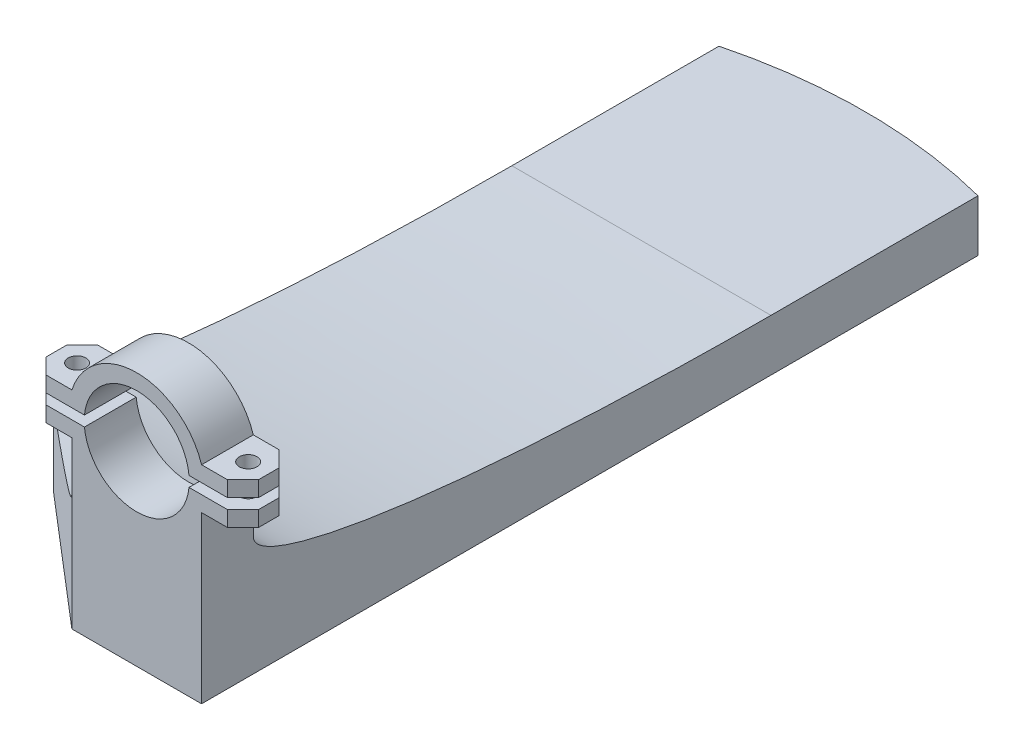
SolidWorks part; units mm, degrees
material "PET"
ref_plane "Front Plane" through (0, 0, 0) normal (0, 0, 1) x (1, 0, 0)
ref_plane "Top Plane" through (0, 0, 0) normal (0, 1, 0) x (1, 0, 0)
ref_plane "Right Plane" through (0, 0, 0) normal (1, 0, 0) x (0, 0, -1)
sketch "Sketch1" plane through (0, 0, 0) normal (0, 0, 1) x (1, 0, 0)
  line L0 (55, 0) -> (-55, 0) construction
  line L1 (-20.5269, -1) -> (-10.1006, -1)
  line L3 (-20.5269, 1) -> (-10.1006, 1)
  line L5 (-27.2535, 0) -> (26.6027, 0) construction
  line L6 (10.1006, 1) -> (20.5269, 1)
  line L7 (-12.5269, 4) -> (-20.5269, 4)
  line L9 (-10.1006, 1) -> (-20.5269, 1)
  line L10 (-20.5269, 4) -> (-20.5269, 1)
  line L11 (-10.1006, -1) -> (-20.5269, -1)
  line L12 (-20.5269, -4) -> (-20.5269, -1)
  line L13 (-12.5269, -4) -> (-20.5269, -4)
  line L15 (0, -55) -> (0, 55) construction
  line L17 (12.5269, -4) -> (20.5269, -4)
  line L18 (20.5269, -4) -> (20.5269, -1)
  line L19 (10.1006, -1) -> (20.5269, -1)
  line L20 (10.1006, 1) -> (20.5269, 1)
  line L21 (20.5269, 4) -> (20.5269, 1)
  line L22 (12.5269, 4) -> (20.5269, 4)
  line L24 (10.1006, 1) -> (20.5269, 1)
  line L25 (20.5269, -1) -> (10.1006, -1)
  line L26 (-20.5269, 1) -> (-10.1006, 1)
  line L27 (-10.1006, -1) -> (-20.5269, -1)
  line L28 (10.1006, -1) -> (20.5269, -1)
  line L31 (-12.5269, -4) -> (-12.5269, -36)
  line L32 (-12.5269, -36) -> (12.5269, -36)
  line L33 (12.5269, -4) -> (12.5269, -36)
  arc A0 (-10.1006, -1) -> (10.1006, -1) centre (0, 0) ccw
  arc A3 (10.1006, 1) -> (-10.1006, 1) centre (0, 0) ccw
  arc A4 (12.5269, 4) -> (-12.5269, 4) centre (0, 0) ccw
  dimension "D1" = 2
  dimension "D2" = 20.3
  dimension "D3" = 3
  dimension "D4" = 8
  dimension "D5" = 3
  dimension "D6" = 32
extrude "Boss-Extrude1" add sketch "Sketch1" along normal mid plane 10 contours L22 A4 L7 L10 L3 A3 L6 L21 | L13 L17 L18 L19 A0 L1 L12 region at (0, -19.9858, 0) region at (-20.0987, 2.5, 0)
sketch "Sketch2" plane through (0, 4, 0) normal (0, 1, 0) x (1, 0, 0)
  line L0 (-20.5269, 5) -> (-12.5269, -5) construction
  line L1 (-20.5269, -5) -> (-12.5269, 5) construction
  line L2 (20.5269, 5) -> (12.5269, -5) construction
  line L3 (20.5269, -5) -> (12.5269, 5) construction
  point P8 (-16.5269, 0)
  point P17 (16.5269, 0)
hole_wizard "M3 Clearance Hole1" positions "Sketch3" profile "Sketch4" hole size "M3" standard "ANSI Metric" end condition through all
sketch "Sketch3" plane through (0, 4, 0) normal (0, 1, 0) x (1, 0, 0)
  point P0 (-16.5269, 0)
  point P3 (16.5269, 0)
sketch "Sketch4" plane through (-16.5269, 4, 0) normal (1, 0, 0) x (0, 0, 1)
  line L0 (0, 0) -> (0, 40)
  line L1 (0, 40) -> (1.7, 40)
  line L2 (1.7, 40) -> (1.7, 0)
  line L5 (1.7, 0) -> (0, 0)
  line L11 (0, -6.35) -> (0, 107.95) construction
  dimension "Thru Hole Dia." = 3.4
  dimension "Thru Hole Depth" = 40
sketch "Sketch5" plane through (0, 0, -5) normal (0, 0, -1) x (-1, 0, 0)
  line L0 (12.5269, -4) -> (12.5269, -36) construction
  line L1 (-12.5269, -36) -> (12.5269, -36)
  line L2 (-12.5269, -36) -> (-12.5269, -26)
  line L3 (-12.5269, -26) -> (12.5269, -26)
  line L4 (12.5269, -36) -> (12.5269, -26)
  dimension "D1" = 10
extrude "Boss-Extrude2" add sketch "Sketch5" along normal blind 140
chamfer "Chamfer2" distance 3 angle 45 4 edges at (-20.5269, 2.5, 5) (-20.5269, 2.5, -5) (20.5269, 2.5, -5) (20.5269, 2.5, 5)
chamfer "Chamfer3" distance 3 angle 45 4 edges at (-20.5269, -2.5, 5) (-20.5269, -2.5, -5) (20.5269, -2.5, 5) (20.5269, -2.5, -5)
sketch "Sketch6" plane through (0, -26, 0) normal (0, 1, 0) x (1, 0, 0)
  line L0 (-12.5269, 145) -> (-12.5269, 5) construction
  line L1 (-37.5269, 145.0139) -> (-37.5269, 16.4107)
  line L2 (-37.5269, 16.4107) -> (-12.5269, -5)
  line L3 (-12.5269, -5) -> (12.5269, 145)
  arc A0 (12.5269, 145) -> (-37.5269, 145.0139) centre (-12.5269, 48.1893) ccw
  dimension "D2" = 100
  dimension "D1" = 25
extrude "Boss-Extrude3" add sketch "Sketch6" against normal up to surface (10 mm away) up to face at (0, -36, -70)
fillet "Fillet1" radius 13 2 edges at (-12.5269, -26, 0) (0, -26, -5) second distance 100 first distance on face at (-12.5269, -15, 0) first distance on face at (0, -8.115, -5)
